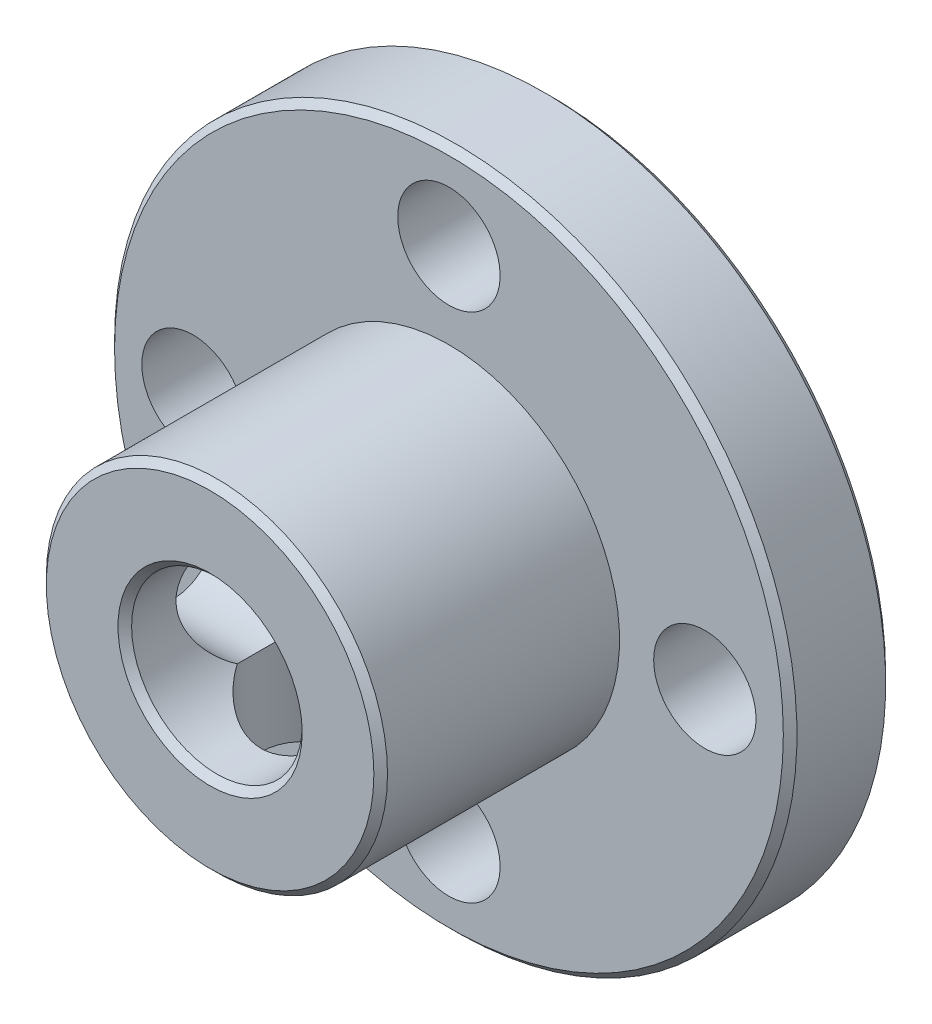
SolidWorks part; units mm, degrees
ref_plane "前视基准面" through (0, 0, 0) normal (0, 0, 1) x (1, 0, 0)
ref_plane "上视基准面" through (0, 0, 0) normal (0, 1, 0) x (1, 0, 0)
ref_plane "右视基准面" through (0, 0, 0) normal (1, 0, 0) x (0, 0, -1)
sketch "草图1" plane through (0, 0, 0) normal (0, 0, 1) x (1, 0, 0)
  circle A0 centre (-0.9003, 2.1984) radius 5
  circle A1 centre (-0.9003, 2.1984) radius 2.5
  dimension "D1" = 10
  dimension "D2" = 5
extrude "凸台-拉伸1" add sketch "草图1" along normal blind 7
sketch "草图2" plane through (0, 0, 0) normal (0, 0, -1) x (-1, 0, 0)
  circle A0 centre (0.9003, 2.1984) radius 2.5
  circle A1 centre (0.9003, 2.1984) radius 10
  circle A2 centre (0.9003, 9.6984) radius 1.5
  circle A3 centre (8.4003, 2.1984) radius 1.5
  circle A4 centre (0.9003, -5.3016) radius 1.5
  circle A5 centre (-6.5997, 2.1984) radius 1.5
  point P7 (0.9003, 2.1984)
  dimension "D1" = 20
  dimension "D2" = 3
  dimension "D4" = 5
  dimension "D5" = 3
  dimension "D6" = 3
  dimension "D7" = 3
  dimension "D3" = 7.5
  dimension "D8" = 7.5
  dimension "D9" = 7.5
  dimension "D10" = 7.5
extrude "凸台-拉伸2" add sketch "草图2" along normal blind 3
chamfer "倒角1" distance 0.2 angle 45 9 edges at (5.0997, 2.1984, -3) (-9.9003, 2.1984, -3) (-3.4003, 2.1984, -3) (-10.9003, 2.1984, -3) (-2.4003, 9.6984, -3) (-2.4003, -5.3016, -3) (4.0997, 2.1984, 7) (1.5997, 2.1984, 7) (-10.9003, 2.1984, 0)
sketch "草图3" plane through (0, 0, 0) normal (0, 1, 0) x (1, 0, 0)
  line L0 (-5.7003, -7) -> (3.8997, -7) construction
  circle A0 centre (-0.9003, -3.5) radius 2
  dimension "D1" = 4
  dimension "D2" = 3.5
extrude "切除-拉伸1" cut sketch "草图3" against normal blind 3 and the other way blind 3
sketch "草图4" plane through (0, 0, 0) normal (1, 0, 0) x (0, 0, -1)
  line L0 (-7, 6.9984) -> (-7, -2.6016) construction
  circle A0 centre (-3.5, 2.1984) radius 2
  dimension "D1" = 4
  dimension "D2" = 3.5
extrude "切除-拉伸2" cut sketch "草图4" against normal blind 6
